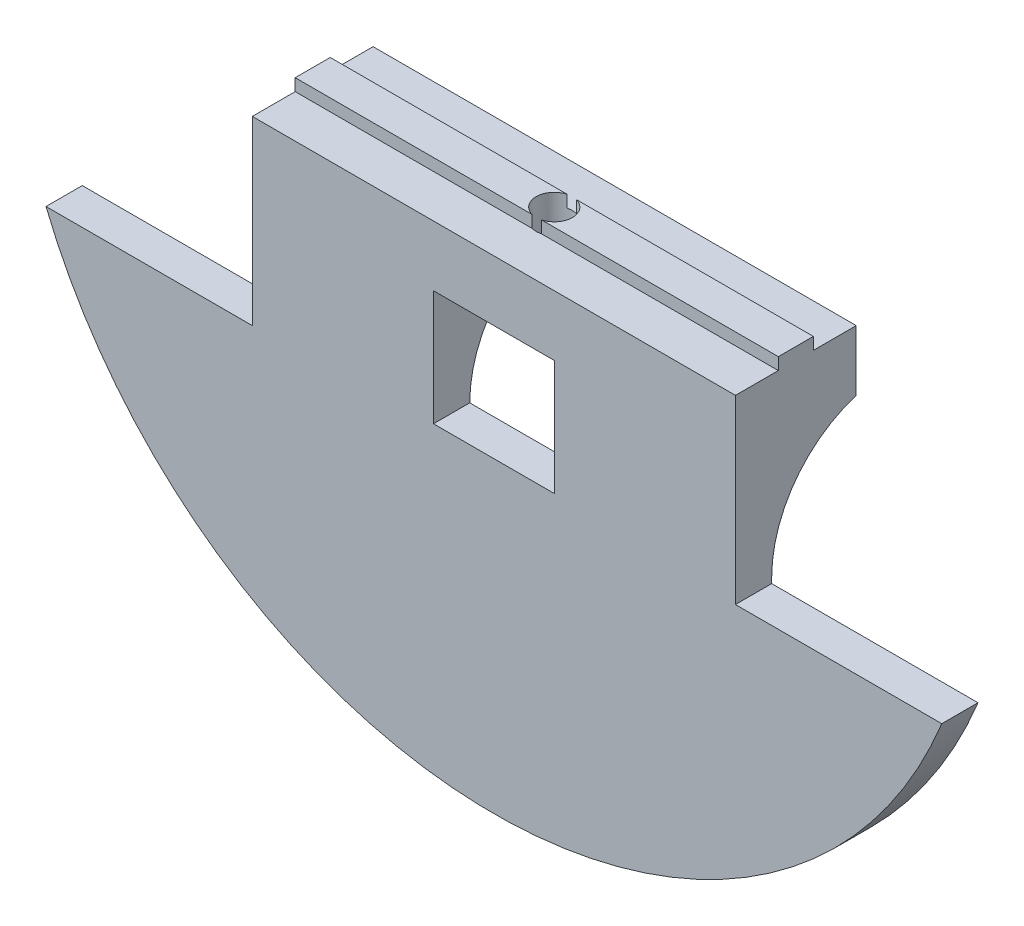
SolidWorks part; units mm, degrees
ref_plane "Front Plane" through (0, 0, 0) normal (0, 0, 1) x (1, 0, 0)
ref_plane "Top Plane" through (0, 0, 0) normal (0, 1, 0) x (1, 0, 0)
ref_plane "Right Plane" through (0, 0, 0) normal (1, 0, 0) x (0, 0, -1)
sketch "Sketch1" plane through (0, 0, 0) normal (0, 0, 1) x (1, 0, 0)
  line L0 (-37.081, -15) -> (-20, -15)
  line L1 (-20, -15) -> (-20, 0)
  line L2 (-20, 0) -> (20, 0)
  line L3 (20, 0) -> (20, -15)
  line L4 (20, -15) -> (37.081, -15)
  arc A0 (37.081, -15) -> (-37.081, -15) centre (0, 0) cw
  point P1 (-3.6409, 35.8615)
  point P8 (54.6538, 38.3518)
  point P9 (-3.6409, 35.907)
  point P10 (0, 0)
  point P12 (20, 5.4167)
  point P13 (20, -15.0131)
  point P14 (20, -2.4065)
  dimension "D2" = 40
  dimension "D1" = 40
  dimension "D3" = 15
extrude "Boss-Extrude1" add sketch "Sketch1" along normal blind 10
sketch "Sketch2" plane through (20, 0, 0) normal (1, 0, 0) x (0, 0, -1)
  line L0 (-10, 0) -> (0, 0) construction
  line L1 (-6.45, 0) -> (-3.55, 0)
  line L2 (-6.45, 0) -> (-6.45, 1)
  line L3 (-6.45, 1) -> (-3.55, 1)
  line L4 (-3.55, 0) -> (-3.55, 1)
  line L5 (-10, -15) -> (-10, 0) construction
  point P4 (-6.1957, 0)
  point P7 (-6.0087, 0.6899)
  dimension "D1" = 2.9
  dimension "D2" = 3.55
  dimension "D3" = 1
extrude "Boss-Extrude2" add sketch "Sketch2" against normal up to surface (40 mm away) up to face at (-20, -7.5, 5)
sketch "Sketch3" plane through (0, 1, 0) normal (0, 1, 0) x (1, 0, 0)
  line L0 (-20, -6.45) -> (-20, -3.55) construction
  circle A0 centre (0, -5) radius 1.5
  point P2 (-20, -5)
  dimension "D1" = 3
extrude "Cut-Extrude1" cut sketch "Sketch3" against normal through all
sketch "Sketch5" plane through (0, 0, 0) normal (1, 0, 0) x (0, 0, -1)
  line L0 (0, 0) -> (0, -15) construction
  line L1 (0, -5) -> (-7, -5)
  line L2 (0, -5) -> (0, -40)
  line L3 (0, -40) -> (-7, -40)
  line L4 (-7, -5) -> (-7, -40)
  line L5 (-3.55, 0) -> (0, 0) construction
  line L6 (-3.5, -40) -> (0, -40) construction
  point P4 (0, -3.9546)
  point P9 (0, -40)
  dimension "D1" = 5
  dimension "D2" = 7
extrude "Cut-Extrude2" cut sketch "Sketch5" against normal through all both and the other way through all
fillet "Fillet1" radius 10 1 edges at (0, -5, 7)
sketch "Sketch6" plane through (0, 0, 0) normal (0, 0, -1) x (-1, 0, 0)
  line L0 (20, -14.5394) -> (-20, -14.5394) construction
  line L1 (-5, -5) -> (5, -5)
  line L2 (-5, -5) -> (-5, -14.5394)
  line L3 (-5, -14.5394) -> (5, -14.5394)
  line L4 (5, -5) -> (5, -14.5394)
  line L5 (20, -5) -> (-20, -5) construction
  point P9 (0, -14.5394)
  dimension "D1" = 10
extrude "Cut-Extrude3" cut sketch "Sketch6" against normal through all
